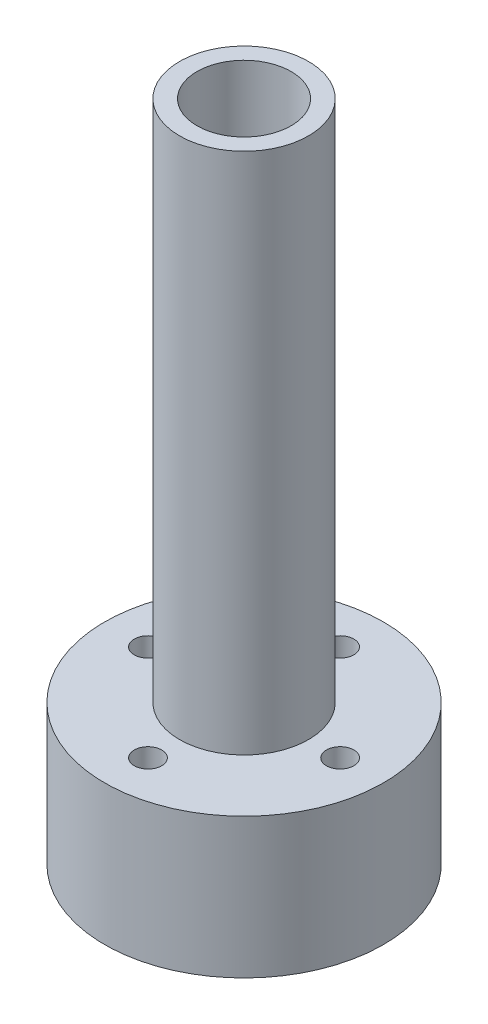
SolidWorks part; units mm, degrees
ref_plane "Front Plane" through (0, 0, 0) normal (0, 0, 1) x (1, 0, 0)
ref_plane "Top Plane" through (0, 0, 0) normal (0, 1, 0) x (1, 0, 0)
ref_plane "Right Plane" through (0, 0, 0) normal (1, 0, 0) x (0, 0, -1)
sketch "Sketch1" plane through (0, 0, 0) normal (0, 1, 0) x (1, 0, 0)
  circle A0 centre (0, 0) radius 10.16
  circle A1 centre (7, 0) radius 1
  circle A2 centre (0, -7) radius 1
  circle A3 centre (-7, 0) radius 1
  circle A4 centre (0, 7) radius 1
  point P5 (-11.5857, -7.1164)
  point P6 (0, 0)
  point P7 (0, 0)
  point P14 (0, 0)
  dimension "D1" = 20.32
  dimension "D2" = 2
  dimension "D3" = 7
  dimension "D4" = 4
extrude "Boss-Extrude1" add sketch "Sketch1" along normal blind 19.05
sketch "Sketch2" plane through (0, 19.05, 0) normal (0, 1, 0) x (1, 0, 0)
  circle A0 centre (0, 0) radius 4.699
  dimension "D1" = 9.398
extrude "Boss-Extrude2" add sketch "Sketch2" along normal blind 57.15 from surface starting at face at (0, 0, 10.16)
sketch "Sketch3" plane through (0, 57.15, 0) normal (0, 1, 0) x (1, 0, 0)
  circle A0 centre (0, 0) radius 3.429
  dimension "D1" = 6.858
extrude "Cut-Extrude1" cut sketch "Sketch3" against normal through all
sketch "Sketch4" plane through (0, 0, 0) normal (0, -1, 0) x (1, 0, 0)
  circle A1 centre (0, 0) radius 10.16
  circle A2 centre (0, 0) radius 10.16
  dimension "D1" = 0
extrude "Cut-Extrude2" cut sketch "Sketch4" against normal blind 8.842
equation "\"D3@Sketch1\"=7MM"
equation "\"D2@Sketch1\"=2MM"
equation "\"tightTol\"= 0.005in"
equation "\"normTol\"= 0.01in"
equation "\"looseTol\"= 0.02in"
equation "\"D1@Sketch2\"=0.375000-\"tightTol\""
equation "\"D1@Sketch3\"=1/4+\"looseTol\""
equation "\"D1@Cut-Extrude2\"= 15.7mm - 0.25 - \"looseTol\""
